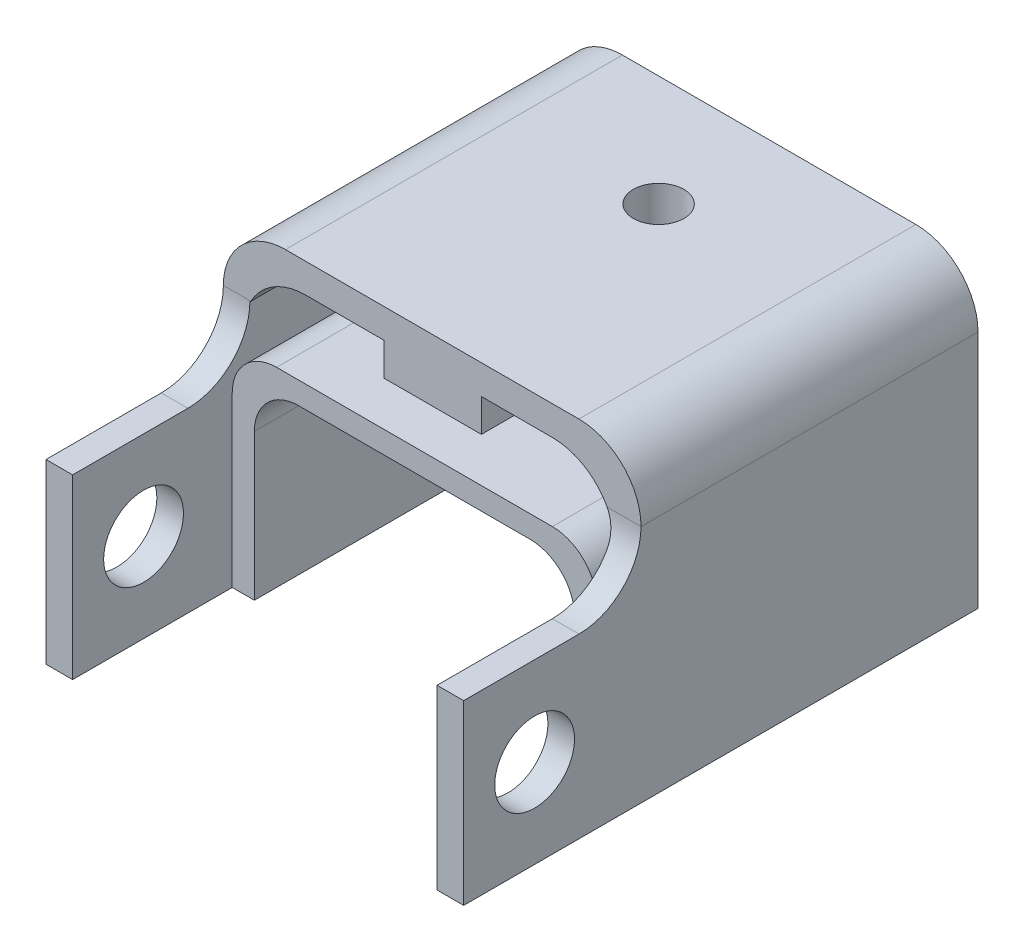
SolidWorks part; units mm, degrees
ref_plane "Front Plane" through (0, 0, 0) normal (0, 0, 1) x (1, 0, 0)
ref_plane "Top Plane" through (0, 0, 0) normal (0, 1, 0) x (1, 0, 0)
ref_plane "Right Plane" through (0, 0, 0) normal (1, 0, 0) x (0, 0, -1)
sketch "Sketch1" plane through (0, 0, 0) normal (1, 0, 0) x (0, 0, -1)
  line L1 (-19, 17) -> (19, 17)
  line L2 (-19, 17) -> (-19, -17)
  line L3 (-19, -17) -> (19, -17)
  line L4 (19, 17) -> (19, -17)
  line L5 (-19, 17) -> (19, -17) construction
  line L6 (-19, -17) -> (19, 17) construction
  point P0 (0, 0)
  dimension "D1" = 38
  dimension "D2" = 34
extrude "Boss-Extrude1" add sketch "Sketch1" along normal blind 23.5 and the other way blind 23.6
sketch "Sketch2" plane through (0, 0, 19) normal (0, 0, 1) x (1, 0, 0)
  line L0 (-23.6, -17) -> (23.5, -17) construction
  line L1 (-20.6, -17) -> (20.5, -17)
  line L2 (-20.6, -17) -> (-20.6, 10)
  line L3 (-20.6, 10) -> (20.5, 10)
  line L4 (20.5, -17) -> (20.5, 10)
  line L5 (-23.6, 17) -> (-23.6, -17) construction
  line L6 (23.5, 17) -> (23.5, -17) construction
  line L7 (-23.6, 17) -> (23.5, 17) construction
  dimension "D1" = 3
  dimension "D2" = 3
  dimension "D3" = 7
extrude "Cut-Extrude1" cut sketch "Sketch2" against normal up to surface (38 mm away) up to face at (-0.05, 0, -19)
fillet "Fillet1" radius 7 2 edges at (23.5, 17, 0) (-23.6, 17, 0)
sketch "Sketch3" plane through (0, 0, 19) normal (0, 0, 1) x (1, 0, 0)
  line L0 (0, 0) -> (0, 15) construction
  line L1 (-16.6, 17) -> (16.5, 17) construction
  line L2 (20.5, 10) -> (-20.6, 10) construction
  line L3 (5.5, 10) -> (-5.5, 10) construction
  line L4 (5.5, 10) -> (5.5, 17) construction
  line L5 (5.5, 17) -> (-5.5, 17) construction
  line L6 (-5.5, 10) -> (-5.5, 17) construction
  line L7 (5.5, 13.7) -> (20.5, 13.7)
  line L8 (20.5, 13.7) -> (20.5, 10)
  line L9 (20.5, 10) -> (5.5, 10)
  line L10 (5.5, 10) -> (5.5, 13.7)
  line L11 (-20.5, 13.7) -> (-20.5, 10)
  line L12 (-5.5, 13.7) -> (-20.5, 13.7)
  line L13 (-5.5, 10) -> (-20.5, 10)
  line L14 (-5.5, 10) -> (-5.5, 13.7)
  dimension "D1" = 11
  dimension "D2" = 15
  dimension "D3" = 5.5
  dimension "D4" = 3.3
extrude "Cut-Extrude2" cut sketch "Sketch3" against normal up to surface (38 mm away) up to face at (-0.05, 0.8899, -19)
fillet "Fillet2" radius 7 2 edges at (-20.5, 13.7, 0) (20.5, 13.7, 0)
sketch "Sketch4" plane through (0, 0, 19) normal (0, 0, 1) x (1, 0, 0)
  line L0 (-20.6, 10) -> (-20.6, -17) construction
  line L1 (-23.6, -17) -> (-20.6, -17)
  line L2 (-23.6, -17) -> (-23.6, 3)
  line L3 (-23.6, 3) -> (-20.6, 3)
  line L4 (-20.6, -17) -> (-20.6, 3)
  line L5 (23.5, 10) -> (23.5, -17) construction
  line L6 (20.5, -17) -> (23.5, -17)
  line L7 (20.5, -17) -> (20.5, 3)
  line L8 (20.5, 3) -> (23.5, 3)
  line L9 (23.5, -17) -> (23.5, 3)
  dimension "D1" = 20
  dimension "D2" = 20
extrude "Boss-Extrude2" add sketch "Sketch4" along normal blind 20
fillet "Fillet3" radius 7 2 edges at (-22.1, 3, 19) (22, 3, 19)
sketch "Sketch5" plane through (0, 0, 0) normal (1, 0, 0) x (0, 0, -1)
  line L0 (-39, -7) -> (19, -7) construction
  line L1 (-39, -17) -> (-39, 3) construction
  line L2 (19, -17) -> (19, 10) construction
  circle A0 centre (-31, -7) radius 4.5
  dimension "D1" = 9
  dimension "D2" = 8
extrude "Cut-Extrude3" cut sketch "Sketch5" against normal up to surface and the other way up to surface up to face at (-23.6, -1.575, 13.925) other way up to face at (23.5, -1.575, 13.925)
sketch "Sketch6" plane through (0, 0, -19) normal (0, 0, -1) x (-1, 0, 0)
  line L0 (20.6, 10) -> (20.6, -17) construction
  line L1 (-20.5, -17) -> (-18, -17)
  line L2 (-20.5, -17) -> (-20.5, 2)
  line L3 (-15.5, 7) -> (15.6, 7)
  line L4 (20.6, -17) -> (20.6, 2)
  line L5 (-5.5, 10) -> (5.5, 10) construction
  line L6 (-18, -17) -> (-18, -0.5)
  line L7 (-13, 4.5) -> (13.1, 4.5)
  line L8 (18.1, -0.5) -> (18.1, -17)
  line L9 (18.1, -17) -> (20.6, -17)
  arc A0 (15.6, 7) -> (20.6, 2) centre (15.6, 2) cw
  arc A1 (-20.5, 2) -> (-15.5, 7) centre (-15.5, 2) cw
  arc A2 (-18, -0.5) -> (-13, 4.5) centre (-13, -0.5) cw
  arc A3 (13.1, 4.5) -> (18.1, -0.5) centre (13.1, -0.5) cw
  point P15 (20.6, 7)
  dimension "D5" = 5
  dimension "D1" = 3
  dimension "D2" = 2.5
  dimension "D3" = 2.5
  dimension "D4" = 2.5
extrude "Boss-Extrude3" add sketch "Sketch6" against normal blind 40
sketch "Sketch7" plane through (0, 0, -19) normal (0, 0, -1) x (-1, 0, 0)
  line L8 (-20.5, 2) -> (-20.5, -17)
  line L9 (-20.5, -17) -> (-18, -17)
  line L10 (-18, -17) -> (-18, -0.5)
  line L11 (-13, 4.5) -> (13.1, 4.5)
  line L12 (18.1, -0.5) -> (18.1, -17)
  line L13 (18.1, -17) -> (20.6, -17)
  line L14 (20.6, -17) -> (20.6, 2)
  line L15 (15.6, 7) -> (-15.5, 7)
  line L16 (-20.5, 2) -> (-20.5, -17)
  line L17 (-20.5, -17) -> (-18, -17)
  line L18 (-18, -17) -> (-18, -0.5)
  line L19 (-13, 4.5) -> (13.1, 4.5)
  line L20 (18.1, -0.5) -> (18.1, -17)
  line L21 (18.1, -17) -> (20.6, -17)
  line L22 (20.6, -17) -> (20.6, 2)
  line L23 (15.6, 7) -> (-15.5, 7)
  arc A4 (-13, 4.5) -> (-18, -0.5) centre (-13, -0.5) ccw
  arc A5 (18.1, -0.5) -> (13.1, 4.5) centre (13.1, -0.5) ccw
  arc A6 (20.6, 2) -> (15.6, 7) centre (15.6, 2) ccw
  arc A7 (-15.5, 7) -> (-20.5, 2) centre (-15.5, 2) ccw
  arc A8 (-13, 4.5) -> (-18, -0.5) centre (-13, -0.5) ccw
  arc A9 (18.1, -0.5) -> (13.1, 4.5) centre (13.1, -0.5) ccw
  arc A10 (20.6, 2) -> (15.6, 7) centre (15.6, 2) ccw
  arc A11 (-15.5, 7) -> (-20.5, 2) centre (-15.5, 2) ccw
  dimension "D1" = 0
extrude "Cut-Extrude4" cut sketch "Sketch7" against normal blind 8
sketch "Sketch8" plane through (-20.6, 0, 0) normal (1, 0, 0) x (0, 0, -1)
  line L0 (11, -0.5) -> (11, -17) construction
  line L1 (11, -17) -> (11, -3)
  arc A0 (11, -17) -> (11, -3) centre (11, -10) ccw
  dimension "D1" = 7
  dimension "D2" = 14
extrude "Boss-Extrude4" add sketch "Sketch8" along normal up to surface (2.5 mm away) up to face at (-18.1, -8.75, 5)
sketch "Sketch9" plane through (20.5, 0, 0) normal (-1, 0, 0) x (0, 0, 1)
  line L1 (-11, -17) -> (-11, -3)
  line L2 (-11, -17) -> (-11, -3)
  arc A1 (-11, -3) -> (-11, -17) centre (-11, -10) ccw
  arc A2 (-11, -3) -> (-11, -17) centre (-11, -10) ccw
  dimension "D1" = 0
extrude "Boss-Extrude5" add sketch "Sketch9" along normal up to surface (2.5 mm away) up to face at (18, -8.75, 5)
sketch "Sketch11" plane through (0, 0, 0) normal (1, 0, 0) x (0, 0, -1)
  arc A0 (11, -17) -> (11, -3) centre (11, -10) ccw construction
  arc A1 (11, -17) -> (11, -3) centre (11, -10) ccw construction
  circle A2 centre (11, -10) radius 8
  dimension "D1" = 1
extrude "Boss-Extrude6" add sketch "Sketch11" against normal up to surface and the other way up to surface separate body up to face at (-18.1, -7.6, 0.4) other way up to face at (18, -7.6, 0.4)
sketch "Sketch12" plane through (0, 17, 0) normal (0, 1, 0) x (1, 0, 0)
  line L0 (0, 0) -> (-0.05, 19) construction
  line L1 (-16.6, 19) -> (16.5, 19) construction
  circle A0 centre (-0.0171, 6.5) radius 2.85
  dimension "D2" = 5.7
  dimension "D1" = 12.5
extrude "Cut-Extrude5" cut sketch "Sketch12" against normal up to surface (7 mm away) up to face at (0, 10, 0)
